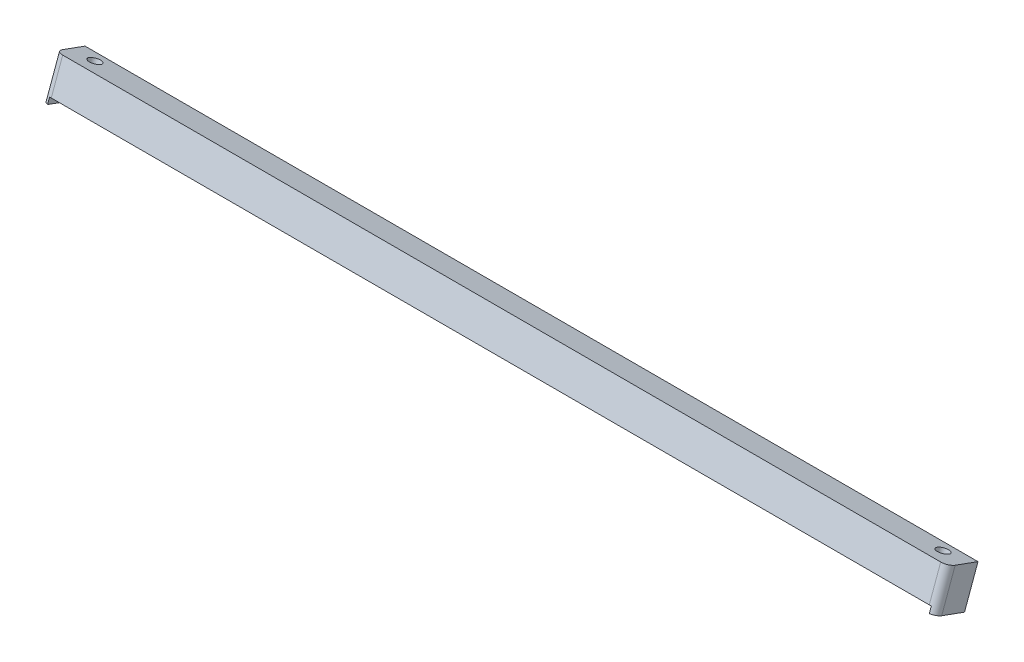
SolidWorks part; units mm, degrees
ref_plane "Front Plane" through (0, 0, 0) normal (0, 0, 1) x (1, 0, 0)
ref_plane "Top Plane" through (0, 0, 0) normal (0, 1, 0) x (1, 0, 0)
ref_plane "Right Plane" through (0, 0, 0) normal (1, 0, 0) x (0, 0, -1)
sketch "Sketch1" plane through (0, 0, 0) normal (1, 0, 0) x (0, 0, -1)
  line L0 (2.5431, 8.3785) -> (-0.1316, 1.0298)
  line L1 (-0.1316, 1.0298) -> (-8.119, 3.937)
  line L3 (3.1176, 9.9569) -> (-4.8698, 12.8641)
  line L5 (-8.119, 3.937) -> (-4.8698, 12.8641)
  line L6 (2.5431, 8.3785) -> (3.1176, 9.9569)
  dimension "D1" = 8.5
  dimension "D2" = 9.5
extrude "Boss-Extrude1" add sketch "Sketch1" along normal blind 239
sketch "Sketch2" plane through (0, 9.7942, -3.5648) normal (0, 0.9397, -0.342) x (1, 0, 0)
  line L0 (119.5, 1.8524) -> (119.5, -8.9759) construction
  line L1 (240, -10.3299) -> (230.3386, -10.3299) construction
  line L2 (240, -10.3299) -> (240, -0.5476) construction
  line L3 (240, -0.5476) -> (230.3386, -0.5476) construction
  line L4 (230.3386, -10.3299) -> (230.3386, -0.5476) construction
  line L6 (239, -8.9759) -> (0, -8.9759) construction
  line L7 (8.6614, -10.3299) -> (8.6614, -0.5476) construction
  line L8 (-1, -0.5476) -> (8.6614, -0.5476) construction
  line L9 (-1, -10.3299) -> (-1, -0.5476) construction
  line L10 (-1, -10.3299) -> (8.6614, -10.3299) construction
  line L11 (6, -4.0476) -> (233, -4.0476) construction
  line L12 (239, -0.4759) -> (0, -0.4759) construction
  circle A0 centre (233, -4.0476) radius 1.6
  circle A1 centre (6, -4.0476) radius 1.6
  point P18 (119.5, -0.4759)
  dimension "D1" = 113.5
extrude "Cut-Extrude1" cut sketch "Sketch2" against normal through all contours A1 | A0 region at (6, 11.1785, 0.2388)
sketch "Sketch3" plane through (0, 0.8671, -0.3156) normal (0, 0.9397, -0.342) x (1, 0, 0)
  line L0 (239, -8.9759) -> (0, -8.9759) construction
  line L1 (0, -0.4759) -> (1.5, -0.4759)
  line L2 (0, -0.4759) -> (0, -8.9759)
  line L3 (0, -8.9759) -> (1.5, -8.9759)
  line L4 (1.5, -0.4759) -> (1.5, -8.9759)
  line L6 (239, -0.4759) -> (237.5, -0.4759)
  line L7 (239, -0.4759) -> (239, -8.9759)
  line L8 (239, -8.9759) -> (237.5, -8.9759)
  line L9 (237.5, -0.4759) -> (237.5, -8.9759)
  dimension "D1" = 1.5
  dimension "D2" = 1.5
extrude "Boss-Extrude2" add sketch "Sketch3" against normal blind 1.6
fillet "Fillet1" radius 2 2 edges at (239, 7.6488, 6.768) (0, 7.6488, 6.768)
sketch "Sketch4" plane through (0, 9.7942, -3.5648) normal (0, 0.9397, -0.342) x (1, 0, 0)
  line L1 (-30.9525, 25.1195) -> (271.8269, 25.1195)
  line L2 (-30.9525, 25.1195) -> (-30.9525, -23.6135)
  line L3 (-30.9525, -23.6135) -> (271.8269, -23.6135)
  line L4 (271.8269, 25.1195) -> (271.8269, -23.6135)
extrude "Cut-Extrude2" cut sketch "Sketch4" against normal blind 0.55
